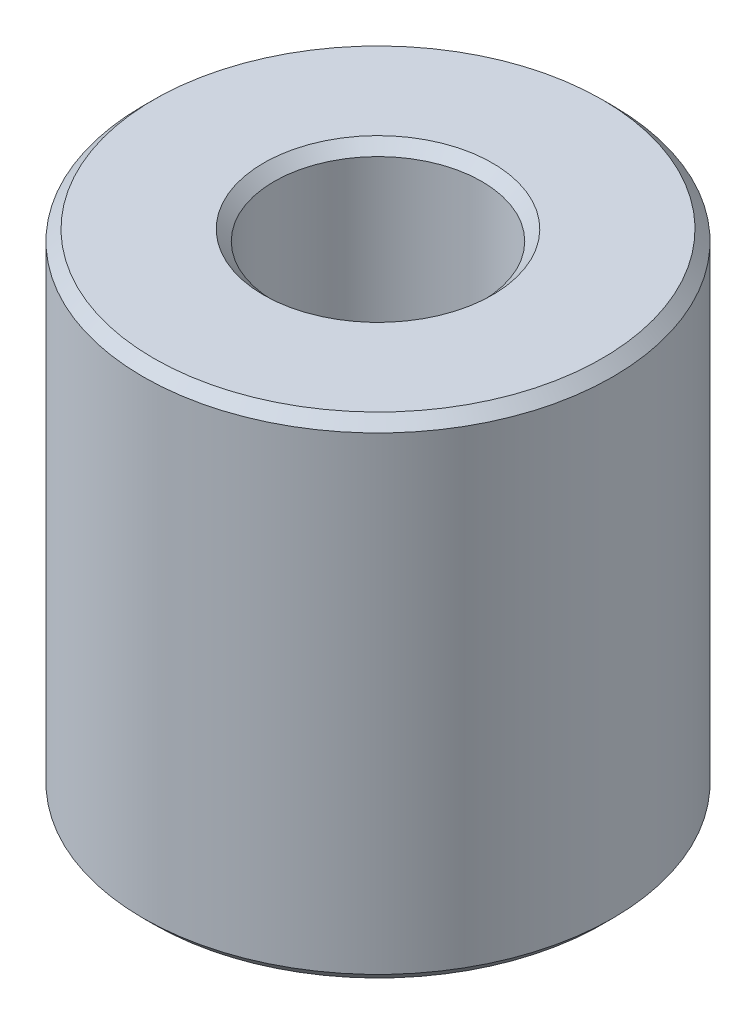
SolidWorks part; units mm, degrees
ref_plane "Front Plane" through (0, 0, 0) normal (0, 0, 1) x (1, 0, 0)
ref_plane "Top Plane" through (0, 0, 0) normal (0, 1, 0) x (1, 0, 0)
ref_plane "Right Plane" through (0, 0, 0) normal (1, 0, 0) x (0, 0, -1)
sketch "Sketch1" plane through (0, 0, 0) normal (0, 1, 0) x (1, 0, 0)
  circle A0 centre (0, 0) radius 40
  dimension "SLEEVE_OD" = 80
extrude "Boss-Extrude1" add sketch "Sketch1" along normal blind 83.4998
sketch "Sketch2" plane through (0, 0, 0) normal (0, 1, 0) x (1, 0, 0)
  circle A0 centre (0, 0) radius 17.6798
  dimension "BORE_D" = 35.3596
extrude "Cut-Extrude1" cut sketch "Sketch2" along normal through all
chamfer "Chamfer1" distance 1.8107 angle 45 4 edges at (0, 83.4998, 17.6798) (0, 0, 17.6798) (0, 0, 40) (0, 83.4998, 40)
